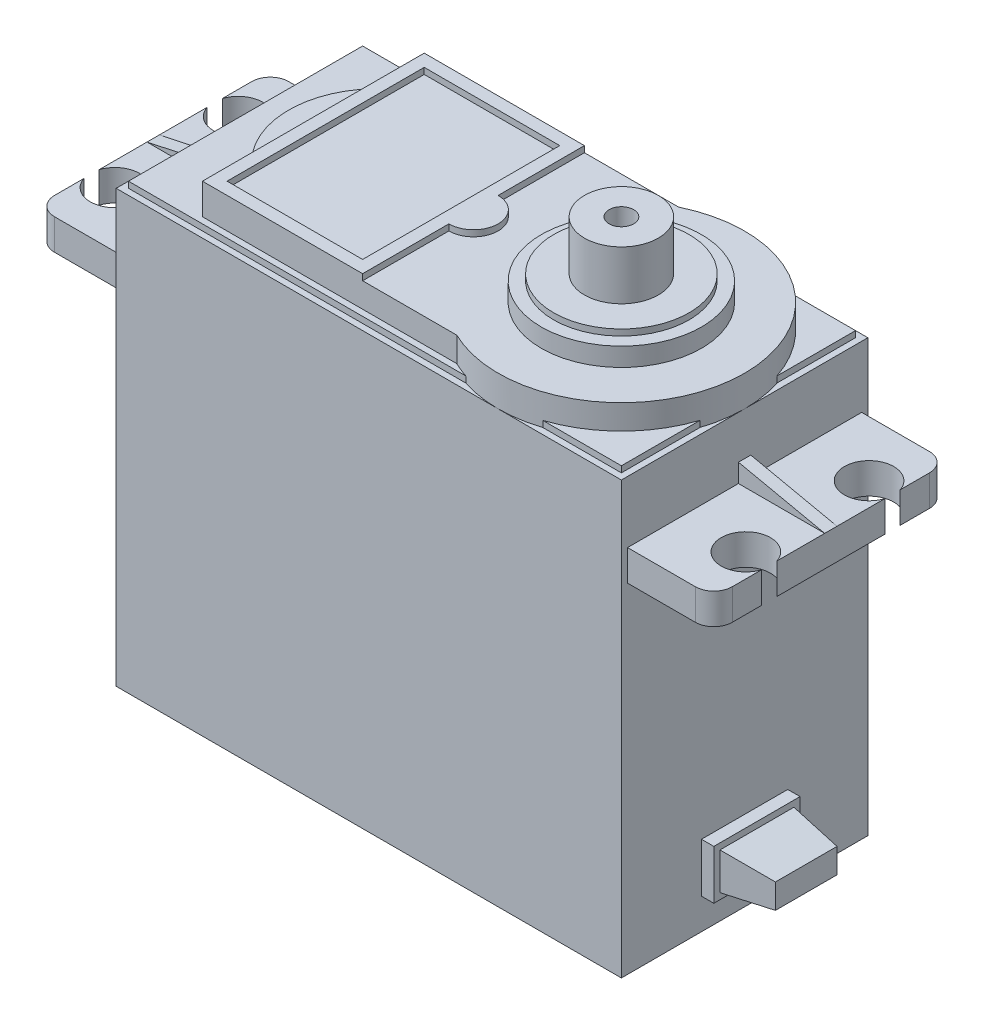
SolidWorks part; units mm, degrees
ref_plane "Front Plane" through (0, 0, 0) normal (0, 0, 1) x (1, 0, 0)
ref_plane "Top Plane" through (0, 0, 0) normal (0, 1, 0) x (1, 0, 0)
ref_plane "Right Plane" through (0, 0, 0) normal (1, 0, 0) x (0, 0, -1)
sketch "Sketch1" plane through (0, 0, 0) normal (0, 1, 0) x (1, 0, 0)
  line L1 (-20.5, -10) -> (20.5, -10)
  line L2 (-20.5, -10) -> (-20.5, 10)
  line L3 (-20.5, 10) -> (20.5, 10)
  line L4 (20.5, -10) -> (20.5, 10)
  line L5 (-20.5, -10) -> (20.5, 10) construction
  line L6 (-20.5, 10) -> (20.5, -10) construction
  point P0 (0, 0)
  dimension "D1" = 41
  dimension "D2" = 20
extrude "Boss-Extrude1" add sketch "Sketch1" along normal blind 40
chamfer "Chamfer1" distance 2 angle 45 4 edges at (20.5, 0, 0) (0, 0, -10) (-20.5, 0, 0) (0, 0, 10)
sketch "Sketch2" plane through (0, 0, 0) normal (0, -1, 0) x (1, 0, 0)
  line L0 (-20.5, 10) -> (20.5, 10) construction
  line L1 (20.5, 10) -> (20.5, -10) construction
  line L2 (20.5, -10) -> (-20.5, -10) construction
  line L3 (-20.5, -10) -> (-20.5, 10) construction
  circle A0 centre (18.25, 7.75) radius 2.25
  circle A1 centre (-18.25, 7.75) radius 2.25
  circle A2 centre (-18.25, -7.75) radius 2.25
  circle A3 centre (18.25, -7.75) radius 2.25
  dimension "D1" = 4.5
  dimension "D2" = 4.5
  dimension "D3" = 4.5
  dimension "D4" = 4.5
extrude "Cut-Extrude1" cut sketch "Sketch2" against normal blind 1
sketch "Sketch3" plane through (20.5, 0, 0) normal (1, 0, 0) x (0, 0, -1)
  line L0 (-10, 40) -> (-10, 2) construction
  line L1 (-9.5, 32) -> (9.5, 32)
  line L2 (-9.5, 32) -> (-9.5, 29.5)
  line L3 (-9.5, 29.5) -> (9.5, 29.5)
  line L4 (9.5, 32) -> (9.5, 29.5)
  line L5 (-10, 40) -> (10, 40) construction
  dimension "D1" = 19
  dimension "D2" = 0.5
  dimension "D3" = 2.5
  dimension "D4" = 8
extrude "Boss-Extrude2" add sketch "Sketch3" along normal blind 7
fillet "Fillet1" radius 1.5 2 edges at (27.5, 30.75, -9.5) (27.5, 30.75, 9.5)
sketch "Sketch4" plane through (0, 32, 0) normal (0, 1, 0) x (1, 0, 0)
  line L0 (20.5, -10) -> (20.5, 10) construction
  line L1 (20.5, 0.5) -> (27.5, 0.5)
  line L2 (20.5, 0.5) -> (20.5, -0.5)
  line L3 (20.5, -0.5) -> (27.5, -0.5)
  line L4 (27.5, 0.5) -> (27.5, -0.5)
  line L5 (27.5, 8) -> (27.5, -8) construction
  line L6 (26, 9.5) -> (20.5, 9.5) construction
  dimension "D1" = 1
  dimension "D2" = 9
extrude "Boss-Extrude3" add sketch "Sketch4" along normal blind 1.5
sketch "Sketch5" plane through (0, 0, 0.5) normal (0, 0, 1) x (1, 0, 0)
  line L0 (27.5, 33.5) -> (27.5, 32) construction
  line L1 (20.5, 33.5) -> (27.5, 33.5) construction
  line L2 (27.5, 33.5) -> (27.5, 32)
  line L3 (20.5, 33.5) -> (27.5, 33.5)
  line L4 (20.5, 33.5) -> (27.5, 32)
extrude "Cut-Extrude2" cut sketch "Sketch5" against normal blind 1
sketch "Sketch6" plane through (0, 32, 0) normal (0, 1, 0) x (1, 0, 0)
  line L2 (27.5, 8) -> (27.5, 0.5) construction
  line L3 (27.5, -0.5) -> (27.5, -8) construction
  line L4 (26, 9.5) -> (20.5, 9.5) construction
  line L5 (26, -9.5) -> (20.5, -9.5) construction
  circle A0 centre (25.6, 5) radius 2
  circle A1 centre (25.6, -5) radius 2
  dimension "D1" = 4
  dimension "D2" = 4
  dimension "D3" = 1.9
  dimension "D4" = 1.9
  dimension "D5" = 4.5
  dimension "D6" = 4.5
extrude "Cut-Extrude3" cut sketch "Sketch6" against normal blind 2.5
mirror "Mirror1" about plane through (0, 0, 0) normal (1, 0, 0) of "Boss-Extrude2", "Fillet1", "Boss-Extrude3", "Cut-Extrude2", "Cut-Extrude3"
sketch "Sketch7" plane through (0, 40, 0) normal (0, 1, 0) x (1, 0, 0)
  line L0 (20.5, 10) -> (-20.5, 10) construction
  line L1 (20.5, -10) -> (20.5, 10) construction
  line L2 (-20.5, -10) -> (20.5, -10) construction
  line L3 (-20.5, 10) -> (-20.5, -10) construction
  line L4 (20.5, 10) -> (-20.5, 10)
  line L5 (20.5, -10) -> (20.5, 10)
  line L6 (-20.5, -10) -> (20.5, -10)
  line L7 (-20.5, 10) -> (-20.5, -10)
extrude "Cut-Extrude4" cut sketch "Sketch7" against normal blind 3
sketch "Sketch8" plane through (0, 37, 0) normal (0, 1, 0) x (1, 0, 0)
  line L0 (20.5, 10) -> (-20.5, 10) construction
  line L1 (-20, -9.5) -> (20, -9.5)
  line L2 (-20, -9.5) -> (-20, 9.5)
  line L3 (-20, 9.5) -> (20, 9.5)
  line L4 (20, -9.5) -> (20, 9.5)
  line L5 (-20, -9.5) -> (20, 9.5) construction
  line L6 (-20, 9.5) -> (20, -9.5) construction
  line L7 (20.5, -0.5) -> (20.5, -9.5) construction
  point P0 (0, 0)
  dimension "D1" = 0.5
  dimension "D2" = 0.5
extrude "Boss-Extrude4" add sketch "Sketch8" along normal blind 0.5
sketch "Sketch9" plane through (0, 37, 0) normal (0, 1, 0) x (1, 0, 0)
  line L0 (20.5, 10) -> (-20.5, 10) construction
  line L1 (20.5, 9.5) -> (20.5, 0.5) construction
  line L2 (6.1411, 9) -> (-14.5, 9)
  line L3 (-14.5, 9) -> (-14.5, 5)
  line L4 (-14.5, -9) -> (6.1411, -9)
  line L5 (-20.5, -10) -> (20.5, -10) construction
  line L6 (-20.5, 9.5) -> (-20.5, 0.5) construction
  line L7 (-14.5, -5) -> (-14.5, -9)
  arc A0 (6.1411, -9) -> (6.1411, 9) centre (10.5, 0) ccw
  arc A1 (-14.5, 5) -> (-14.5, -5) centre (-9.25, 0) ccw
  point P15 (-16.5, 0)
  point P16 (-14.5, 5)
  point P17 (-14.5, -5)
  point P18 (0, 0)
  point P19 (0, 0)
  dimension "D1" = 20
  dimension "D5" = 2
  dimension "D2" = 1
  dimension "D3" = 1
  dimension "D4" = 6
  dimension "D6" = 10
extrude "Boss-Extrude6" add sketch "Sketch9" along normal blind 2.5
sketch "Sketch10" plane through (0, 39.5, 0) normal (0, 1, 0) x (1, 0, 0)
  line L0 (6.1411, 9) -> (-14.5, 9) construction
  line L1 (-14.5, 9) -> (-1.5, 9)
  line L2 (-14.5, 9) -> (-14.5, -9)
  line L3 (-14.5, -9) -> (-1.5, -9)
  line L4 (-1.5, 9) -> (-1.5, 2)
  line L5 (-14.5, -9) -> (6.1411, -9) construction
  line L6 (-14.5, 9) -> (-14.5, 5) construction
  line L7 (-1.5, -2) -> (-1.5, -9)
  line L9 (-13.5, 8) -> (-2.5, 8)
  line L10 (-13.5, 8) -> (-13.5, -8)
  line L11 (-13.5, -8) -> (-2.5, -8)
  line L12 (-2.5, 8) -> (-2.5, -8)
  arc A0 (-1.5, -2) -> (-1.5, 2) centre (-1.5, 0) ccw
  dimension "D5" = 4
  dimension "D1" = 13
  dimension "D2" = 0
  dimension "D3" = 0
  dimension "D4" = 0
  dimension "D6" = 1
  dimension "D7" = 1
  dimension "D8" = 1
  dimension "D9" = 1
extrude "Boss-Extrude7" add sketch "Sketch10" along normal blind 0.5
sketch "Sketch11" plane through (0, 39.5, 0) normal (0, 1, 0) x (1, 0, 0)
  circle A0 centre (10.5, 0) radius 6.5
  dimension "D1" = 13
extrude "Boss-Extrude8" add sketch "Sketch11" along normal blind 1.5
sketch "Sketch12" plane through (0, 41, 0) normal (0, 1, 0) x (1, 0, 0)
  circle A0 centre (10.5, 0) radius 5.5
  dimension "D1" = 11
extrude "Boss-Extrude9" add sketch "Sketch12" along normal blind 0.5
sketch "Sketch13" plane through (0, 41.5, 0) normal (0, 1, 0) x (1, 0, 0)
  circle A0 centre (10.5, 0) radius 3
  dimension "D1" = 6
extrude "Boss-Extrude10" add sketch "Sketch13" along normal blind 4
sketch "Sketch14" plane through (0, 45.5, 0) normal (0, 1, 0) x (1, 0, 0)
  circle A0 centre (10.5, 0) radius 1
  dimension "D1" = 2
extrude "Cut-Extrude5" cut sketch "Sketch14" against normal blind 8
sketch "Sketch15" plane through (20.5, 0, 0) normal (1, 0, 0) x (0, 0, -1)
  line L0 (5.5139, 0) -> (-5.5139, 0) construction
  line L1 (-3.5, 8.5) -> (3.5, 8.5)
  line L2 (-3.5, 8.5) -> (-3.5, 4.5)
  line L3 (-3.5, 4.5) -> (3.5, 4.5)
  line L4 (3.5, 8.5) -> (3.5, 4.5)
  line L5 (-10, 37) -> (-10, 2) construction
  dimension "D1" = 4.5
  dimension "D2" = 7
  dimension "D3" = 4
  dimension "D4" = 6.5
extrude "Boss-Extrude11" add sketch "Sketch15" along normal blind 5
sketch "Sketch16" plane through (25.5, 0, 0) normal (1, 0, 0) x (0, 0, -1)
  line L0 (3.5, 8.5) -> (-3.5, 8.5) construction
  line L1 (-3, 8) -> (3, 8)
  line L2 (-3, 8) -> (-3, 5)
  line L3 (-3, 5) -> (3, 5)
  line L4 (3, 8) -> (3, 5)
  line L5 (-3.5, 4.5) -> (3.5, 4.5) construction
  line L6 (3.5, 4.5) -> (3.5, 8.5) construction
  line L7 (-3.5, 8.5) -> (-3.5, 4.5) construction
  line L8 (-3.5, 8.5) -> (-3.5, 4.5) construction
  line L9 (3.5, 8.5) -> (-3.5, 8.5) construction
  line L10 (-3.5, 8.5) -> (-3.5, 4.5)
  line L11 (-3.5, 4.5) -> (3.5, 4.5)
  line L12 (3.5, 4.5) -> (3.5, 8.5)
  line L13 (3.5, 8.5) -> (-3.5, 8.5)
  dimension "D1" = 0.5
  dimension "D2" = 0.5
  dimension "D3" = 0.5
  dimension "D4" = 0.5
extrude "Cut-Extrude6" cut sketch "Sketch16" against normal blind 4
sketch "Sketch17" plane through (0, 5, 0) normal (0, -1, 0) x (1, 0, 0)
  line L0 (21.5, 3) -> (25.5, 2.5)
  line L1 (25.5, 3) -> (25.5, -3) construction
  line L2 (21.5, -3) -> (25.5, -2.5)
  line L3 (21.5, -3) -> (25.5, -3) construction
  line L4 (21.5, 3) -> (25.5, 3) construction
  line L5 (21.5, -3) -> (25.5, -3)
  line L6 (25.5, 3) -> (25.5, 2.5)
  line L7 (21.5, 3) -> (25.5, 3)
  line L8 (25.5, -2.5) -> (25.5, -3)
  dimension "D1" = 0.5
  dimension "D2" = 0.5
extrude "Cut-Extrude7" cut sketch "Sketch17" against normal blind 3
sketch "Sketch18" plane through (0, 0, -3.5) normal (0, 0, -1) x (-1, 0, 0)
  line L0 (-21.5, 8) -> (-25.5, 8)
  line L1 (-25.5, 8) -> (-25.5, 7.5)
  line L2 (-25.5, 8) -> (-25.5, 5) construction
  line L3 (-25.5, 7.5) -> (-21.5, 8)
  line L4 (-21.5, 5) -> (-25.5, 5)
  line L5 (-25.5, 5) -> (-25.5, 5.5)
  line L6 (-25.5, 5.5) -> (-21.5, 5)
  dimension "D1" = 0.5
  dimension "D2" = 0.5
extrude "Cut-Extrude8" cut sketch "Sketch18" against normal blind 7
